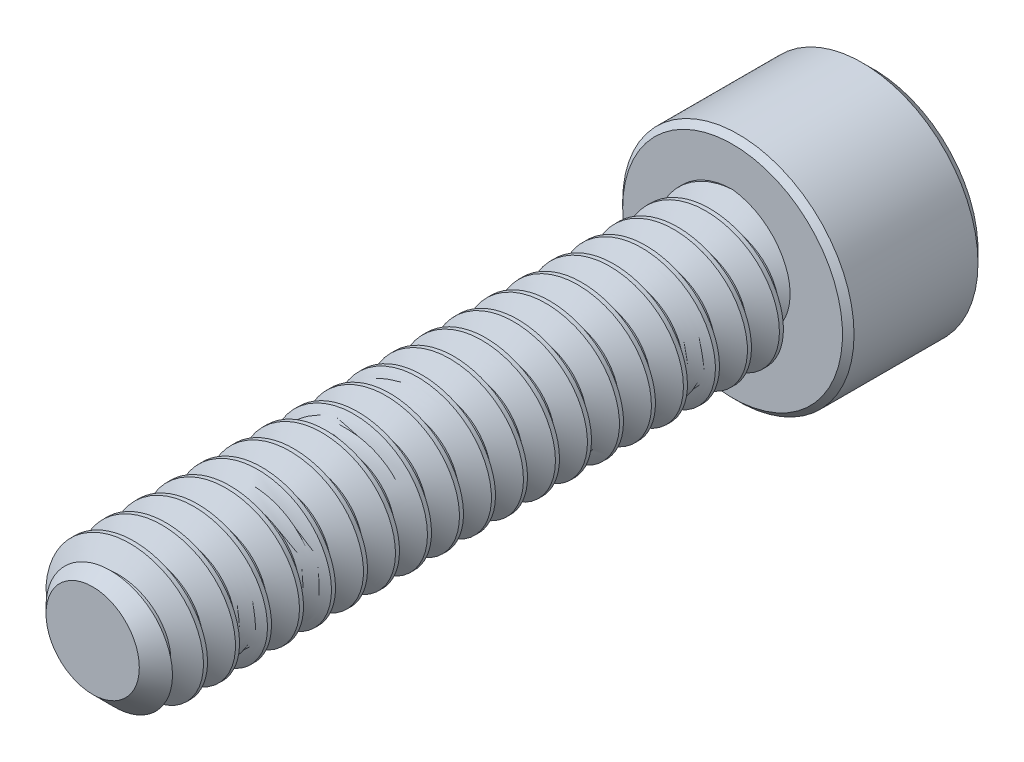
SolidWorks part; units mm, degrees
ref_plane "Front Plane" through (0, 0, 0) normal (0, 0, 1) x (1, 0, 0)
ref_plane "Top Plane" through (0, 0, 0) normal (0, 1, 0) x (1, 0, 0)
ref_plane "Right Plane" through (0, 0, 0) normal (1, 0, 0) x (0, 0, -1)
sketch "Sketch0" plane through (0, 0, 0) normal (1, 0, 0) x (0, 0, -1)
  line L0 (0, 0) -> (15.875, 0) construction
  point P2 (19.3802, 0)
  point P4 (0, 0)
  dimension "D1" = 15.875
  dimension "D2" = 3.5052
  dimension "Min Thread" = 0
sketch "Sketch1" plane through (0, 0, 0) normal (0, 0, 1) x (1, 0, 0)
  circle A0 centre (0, 0) radius 1.7526
  dimension "OD" = 3.5052
extrude "Extrude1" add sketch "Sketch1" against normal blind 15.875
sketch "Sketch2" plane through (0, 0, 0) normal (0, 0, 1) x (1, 0, 0)
  circle A0 centre (0, 0) radius 1.7526 construction
  circle A1 centre (0, 0) radius 1.7526
curve "Helix/Spiral1" pitch 0.7937 height 16.6687 turns 21 parameters "pitch"=0.7937
chamfer "Chamfer3" distance 0.5953 angle 45 1 edges at (1.7526, 0, 0)
sketch "Sketch3" plane through (0, 0, 0) normal (1, 0, 0) x (0, 0, -1)
  line L0 (-0.6945, 1.7526) -> (-0.3969, 1.237)
  line L1 (-0.3969, 1.237) -> (-0.2977, 1.237)
  line L2 (-0.2977, 1.237) -> (0, 1.7526)
  line L3 (-0.6945, 1.7526) -> (0, 1.7526)
  line L4 (-0.3473, 1.7526) -> (-0.3473, 1.237) construction
  line L5 (-0.5457, 1.4948) -> (-0.1488, 1.4948) construction
  line L6 (0, 1.7526) -> (0, -1.7526) construction
  dimension "D1" = 0.0992
  dimension "D2" = 0.3969
  dimension "D3" = 60
sweep "Cut-Sweep1" cut profiles "Sketch3" path "Helix/Spiral1"
sketch "Sketch5" plane through (0, 0, 0) normal (1, 0, 0) x (0, 0, -1)
  line L0 (15.875, -1.2539) -> (15.875, 1.2505) construction
  line L1 (15.875, 1.7526) -> (0, 1.7526)
  line L2 (15.875, 1.7526) -> (15.875, 0)
  line L3 (15.875, 0) -> (-0.6379, 0)
  line L4 (0, 0) -> (15.875, 0) construction
  line L5 (0, 1.7526) -> (-0.6379, 0)
  line L6 (0, 0) -> (18.415, 0) construction
  dimension "D1" = 70
  dimension "D3" = 2.54
revolve "partially thread" [suppressed] add sketch "Sketch5" angle 360 about L6
sketch "Sketch6" plane through (0, 0, -15.875) normal (0, 0, -1) x (-1, 0, 0)
  circle A0 centre (0, 0) radius 2.8702
  dimension "head dia" = 5.7404
extrude "Extrude2" add sketch "Sketch6" along normal blind 3.5052
sketch "Sketch7" plane through (0, 0, -19.3802) normal (0, 0, -1) x (-1, 0, 0)
  line L1 (0, 1.604) -> (-1.3891, 0.802)
  line L2 (-1.3891, 0.802) -> (-1.3891, -0.802)
  line L3 (-1.3891, -0.802) -> (0, -1.604)
  line L4 (0, -1.604) -> (1.3891, -0.802)
  line L5 (1.3891, -0.802) -> (1.3891, 0.802)
  line L6 (1.3891, 0.802) -> (0, 1.604)
  circle A0 centre (0, 0) radius 1.3891 construction
  dimension "hex dia" = 2.7781
extrude "Cut-Extrude1" cut sketch "Sketch7" against normal blind 2.0836
sketch "Sketch8" plane through (0, 0, -19.3802) normal (0, 0, -1) x (-1, 0, 0)
  circle A0 centre (0, 0) radius 1.604
extrude "Cut-Extrude2" cut sketch "Sketch8" against normal through all draft 45
chamfer "Chamfer1" distance 0.287 angle 45 1 edges at (-2.8702, 0, -19.3802)
chamfer "Chamfer2" distance 0.1435 angle 45 1 edges at (-2.8702, 0, -15.875)
sketch "Sketch9" plane through (0, 0, 0) normal (1, 0, 0) x (0, 0, -1)
  line L0 (0, 1.7526) -> (0, -1.7526) construction
  line L1 (1.9844, 1.7526) -> (1.9844, -1.7526) construction
  line L2 (19.3802, 2.8702) -> (19.3802, -2.8702) construction
  line L3 (15.875, 2.8702) -> (15.875, -2.8702) construction
  line L4 (15.875, 2.7267) -> (15.875, -2.7267) construction
  line L5 (19.3802, -2.5832) -> (19.3802, 2.5832) construction
  line L6 (15.875, -2.8702) -> (15.875, 2.8702) construction
  line L7 (0, 1.1573) -> (0, -1.1573) construction
  line L8 (-0.6945, 1.7526) -> (0, 1.7526) construction
  line L9 (1.9844, 0) -> (0, 0) construction
  dimension "D1" = 1.9844
equation "\"D3@Helix/Spiral1\" = \"screw length@Extrude1\"+\"pitch@Helix/Spiral1\""
equation "\"D1@Sketch3\" = \"pitch@Helix/Spiral1\"*.125"
equation "\"D2@Sketch3\" = \"pitch@Helix/Spiral1\"*.5"
equation "\"D1@Cut-Extrude1\" = \"hex dia@Sketch7\"*.75"
equation "\"D1@Chamfer1\" = \"head dia@Sketch6\"*.05"
equation "\"D1@Sketch9\" = \"pitch@Helix/Spiral1\"*2.50"
equation "\"D1@Chamfer2\" = \"D1@Chamfer1\"/2"
equation "\"D1@Chamfer3\" = \"pitch@Helix/Spiral1\"*.750"
equation "\"D1@Sketch0\" = \"screw length@Extrude1\""
equation "\"D2@Sketch0\" = \"head depth@Extrude2\""
